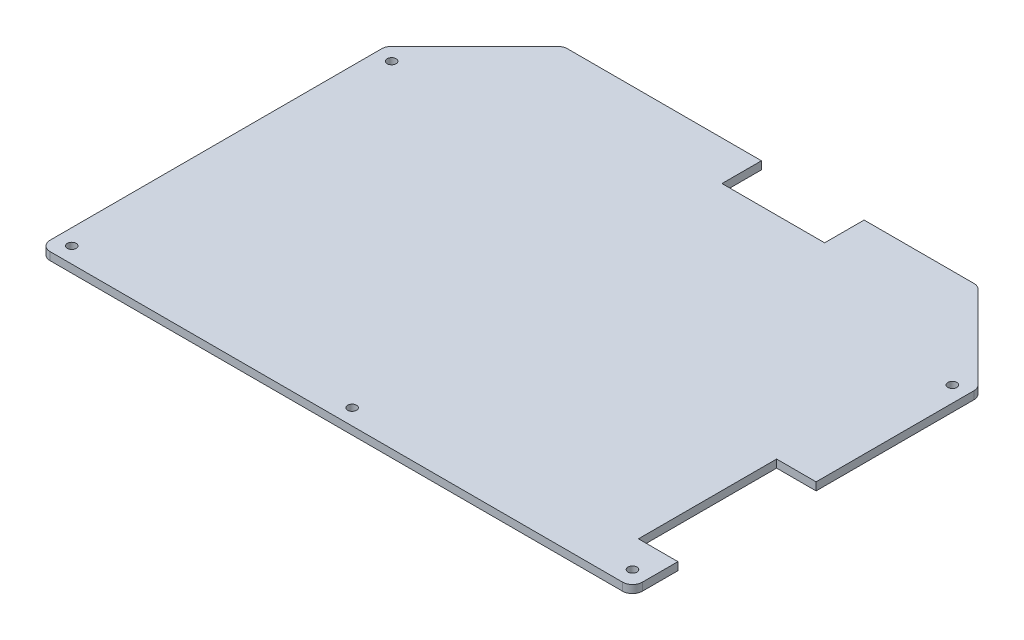
SolidWorks part; units mm, degrees
material "Acier non allié"
ref_plane "Front" through (0, 0, 0) normal (0, 0, 1) x (1, 0, 0)
ref_plane "Top" through (0, 0, 0) normal (0, 1, 0) x (1, 0, 0)
ref_plane "Right" through (0, 0, 0) normal (1, 0, 0) x (0, 0, -1)
sketch "Main scetch" plane through (0, 0, 0) normal (0, 1, 0) x (1, 0, 0)
  line L0 (-150, 0) -> (150, 0)
  line L1 (0, 0) -> (150, 0) construction
  line L2 (0, 0) -> (0, 220) construction
  line L3 (0, 220) -> (150, 220) construction
  line L4 (150, 0) -> (150, 220) construction
  line L5 (150, 0) -> (150, 175)
  line L6 (150, 175) -> (105, 220)
  line L10 (105, 220) -> (-105, 220)
  line L11 (-150, 0) -> (-150, 175)
  line L12 (-150, 175) -> (-105, 220)
  dimension "D1" = 150
  dimension "D2" = 220
  dimension "D3" = 45
  dimension "D4" = 45
extrude "Main extrusion" add sketch "Main scetch" along normal blind 4
fillet "Corner leave" radius 5 6 edges at (-150, 2, 0) (150, 2, -175) (105, 2, -220) (150, 2, 0) (-105, 2, -220) (-150, 2, -175)
sketch "Esquisse1" plane through (0, 4, 0) normal (0, 1, 0) x (1, 0, 0)
  line L0 (-145, 0) -> (145, 0) construction
  line L1 (-150, 172.9289) -> (-150, 5) construction
  line L3 (0, 0) -> (0, 62.3031) construction
  line L4 (150, 5) -> (150, 172.9289) construction
  circle A0 centre (-142, 8) radius 1
  circle A1 centre (-142, 170) radius 1
  circle A4 centre (142, 170) radius 1
  circle A5 centre (142, 8) radius 1
  circle A6 centre (0, 8) radius 1.5
  dimension "D3" = 2
  dimension "D6" = 2
  dimension "D8" = 8
  dimension "D15" = 2
  dimension "D18" = 2
  dimension "D7" = 3
  dimension "D1" = 8
  dimension "D2" = 8
  dimension "D4" = 8
  dimension "D5" = 170
  dimension "D13" = 170
  dimension "D14" = 8
  dimension "D16" = 8
  dimension "D17" = 8
hole_wizard "Dégagement M41" positions "Esquisse2" profile "Esquisse3" hole size "M4" standard "ISO" end condition through all
sketch "Esquisse2" plane through (0, 4, 0) normal (0, 1, 0) x (1, 0, 0)
  point P0 (-142, 8)
  point P3 (-142, 170)
  point P6 (142, 170)
  point P9 (142, 8)
  point P12 (0, 8)
sketch "Esquisse3" plane through (-142, 4, -8) normal (1, 0, 0) x (0, 0, 1)
  line L0 (0, 0) -> (0, 4)
  line L1 (0, 4) -> (2.25, 4)
  line L2 (2.25, 4) -> (2.25, 0)
  line L5 (2.25, 0) -> (0, 0)
  line L11 (0, -6.35) -> (0, 107.95) construction
  dimension "Diamètre du perçage jusqu'au prochain" = 4.5
  dimension "Profondeur du perçage jusqu'au prochain" = 4
sketch "Esquisse4" plane through (0, 4, 0) normal (0, 1, 0) x (1, 0, 0)
  line L0 (150, 5) -> (150, 172.9289) construction
  line L3 (130, 23) -> (150, 23)
  line L5 (-145, 0) -> (145, 0) construction
  line L7 (130, 93) -> (150, 93)
  line L8 (130, 93) -> (130, 23)
  line L10 (150, 93) -> (150, 23)
  point P0 (150, 24.4206)
  dimension "D1" = 23
  dimension "D2" = 70
  dimension "D6" = 20
extrude "Enlèv. mat.-Extru.1" cut sketch "Esquisse4" against normal up to surface (4 mm away) up to face at (-142, 0, -5.75)
sketch "Esquisse5" plane through (0, 4, 0) normal (0, 1, 0) x (1, 0, 0)
  line L0 (150, 93) -> (150, 172.9289) construction
  line L3 (35.62, 200) -> (47.32, 200)
  line L4 (47.32, 220) -> (47.32, 200)
  line L5 (102.9289, 220) -> (-102.9289, 220) construction
  line L7 (-4.68, 220) -> (47.32, 220)
  line L8 (-4.68, 220) -> (-4.68, 200)
  line L9 (-4.68, 200) -> (35.62, 200)
  point P6 (34.8358, 200)
  point P10 (0, 0)
  point P12 (47.5807, 220)
  point P13 (34.9449, 220)
  point P14 (47.1257, 220)
  dimension "D1" = 102.68
  dimension "D2" = 52
  dimension "D5" = 20
extrude "Enlèv. mat.-Extru.2" cut sketch "Esquisse5" against normal up to surface (4 mm away) up to face at (-142, 0, -5.75)
equation "\"WIDTH\"= 300mm'Total width of the robot"
equation "\"LENGTH\"= 220mm'Total length of the robot"
equation "\"D1@Main scetch\" = \"WIDTH\" / 2"
equation "\"D2@Main scetch\" = \"LENGTH\""
equation "\"CUT_DEPTH\"= 45mm'Depth of the cut on the edges of the plate"
equation "\"D3@Main scetch\" = \"CUT_DEPTH\""
equation "\"D4@Main scetch\" = \"CUT_DEPTH\""
equation "\"Plate_th\"= 3mm'Thickness of the plate"
equation "\"D1\"= \"Plate_th\""
